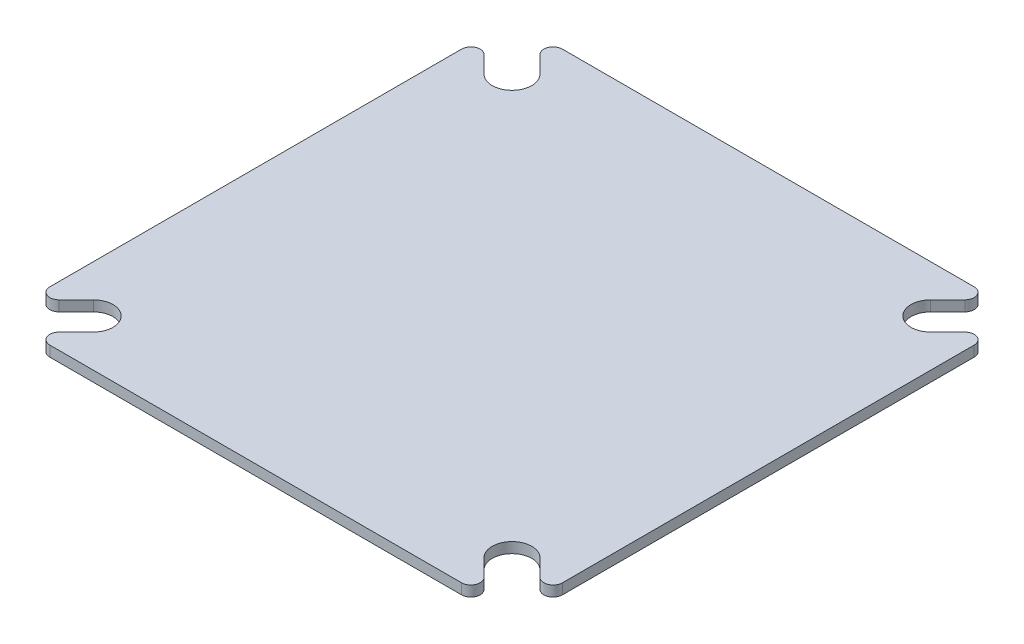
SolidWorks part; units mm, degrees
ref_plane "Front Plane" through (0, 0, 0) normal (0, 0, 1) x (1, 0, 0)
ref_plane "Top Plane" through (0, 0, 0) normal (0, 1, 0) x (1, 0, 0)
ref_plane "Right Plane" through (0, 0, 0) normal (1, 0, 0) x (0, 0, -1)
ref_axis "Axis1" through (0, 0, 0) along (0, 1, 0)
sketch "Sketch1" plane through (0, 0, 0) normal (0, 1, 0) x (1, 0, 0)
  line L0 (0, 139.7) -> (0, -139.7) construction
  line L1 (139.7, -139.7) -> (-139.7, -139.7)
  line L2 (139.7, -139.7) -> (139.7, 139.7)
  line L3 (139.7, 139.7) -> (-139.7, 139.7)
  line L4 (-139.7, -139.7) -> (-139.7, 139.7)
  line L5 (139.7, -139.7) -> (-139.7, 139.7) construction
  line L6 (139.7, 139.7) -> (-139.7, -139.7) construction
  line L7 (-139.7, 0) -> (139.7, 0) construction
  point P0 (0, 0)
  dimension "D1" = 279.4
  dimension "D2" = 279.4
extrude "Boss-Extrude1" add sketch "Sketch1" along normal blind 5.715
sketch "Sketch6" plane through (0, 5.715, 0) normal (0, 1, 0) x (1, 0, 0)
  line L0 (139.7, -139.7) -> (-139.7, 139.7) construction
  line L1 (139.7, 139.7) -> (-139.7, 139.7) construction
  line L2 (0, -62.226) -> (0, 62.226) construction
  line L3 (-62.226, 0) -> (62.226, 0) construction
  circle A0 centre (-114.3, 114.3) radius 5.0419
  circle A1 centre (114.3, 114.3) radius 5.0419
  circle A2 centre (114.3, -114.3) radius 5.0419
  circle A3 centre (-114.3, -114.3) radius 5.0419
  dimension "D1" = 10.0838
  dimension "D2" = 25.4
extrude "Cut-Extrude4" cut sketch "Sketch6" against normal up to next
sketch "Sketch8" plane through (0, 5.715, 0) normal (0, 1, 0) x (1, 0, 0)
  line L0 (-139.7, 139.7) -> (-139.7, 124.46)
  line L1 (-139.7, -139.7) -> (-139.7, 139.7) construction
  line L2 (-139.7, 139.7) -> (-124.46, 139.7)
  line L3 (139.7, 139.7) -> (-139.7, 139.7) construction
  line L4 (-139.7, 124.46) -> (-121.7395, 106.4995)
  line L5 (139.7, -139.7) -> (-139.7, 139.7) construction
  line L6 (-124.46, 139.7) -> (-106.4995, 121.7395)
  line L8 (-3.1432, 0) -> (3.1432, 0) construction
  line L9 (-124.46, -139.7) -> (-106.4995, -121.7395)
  line L10 (-139.7, -124.46) -> (-121.7395, -106.4995)
  line L11 (-139.7, -139.7) -> (-124.46, -139.7)
  line L12 (-139.7, -139.7) -> (-139.7, -124.46)
  line L13 (0, -3.1432) -> (0, 3.1432) construction
  line L14 (139.7, -139.7) -> (139.7, -124.46)
  line L15 (139.7, -139.7) -> (124.46, -139.7)
  line L16 (139.7, -124.46) -> (121.7395, -106.4995)
  line L17 (124.46, -139.7) -> (106.4995, -121.7395)
  line L18 (124.46, 139.7) -> (106.4995, 121.7395)
  line L19 (139.7, 124.46) -> (121.7395, 106.4995)
  line L20 (139.7, 139.7) -> (124.46, 139.7)
  line L21 (139.7, 139.7) -> (139.7, 124.46)
  arc A1 (-121.7395, 106.4995) -> (-106.4995, 121.7395) centre (-114.1195, 114.1195) ccw
  arc A2 (-121.7395, -106.4995) -> (-106.4995, -121.7395) centre (-114.1195, -114.1195) cw
  arc A3 (121.7395, -106.4995) -> (106.4995, -121.7395) centre (114.1195, -114.1195) ccw
  arc A4 (121.7395, 106.4995) -> (106.4995, 121.7395) centre (114.1195, 114.1195) cw
  dimension "D1" = 15.24
  dimension "D2" = 25.4
  dimension "D3" = 25.4
extrude "Cut-Extrude6" cut sketch "Sketch8" against normal up to next
fillet "Fillet1" radius 5.08 8 edges at (124.46, 2.8575, 139.7) (139.7, 2.8575, 124.46) (-124.46, 2.8575, 139.7) (-139.7, 2.8575, 124.46) (139.7, 2.8575, -124.46) (124.46, 2.8575, -139.7) (-139.7, 2.8575, -124.46) (-124.46, 2.8575, -139.7)
equation "\"t\"= 0.225"
equation "\"D1@Boss-Extrude1\"=\"t\""
